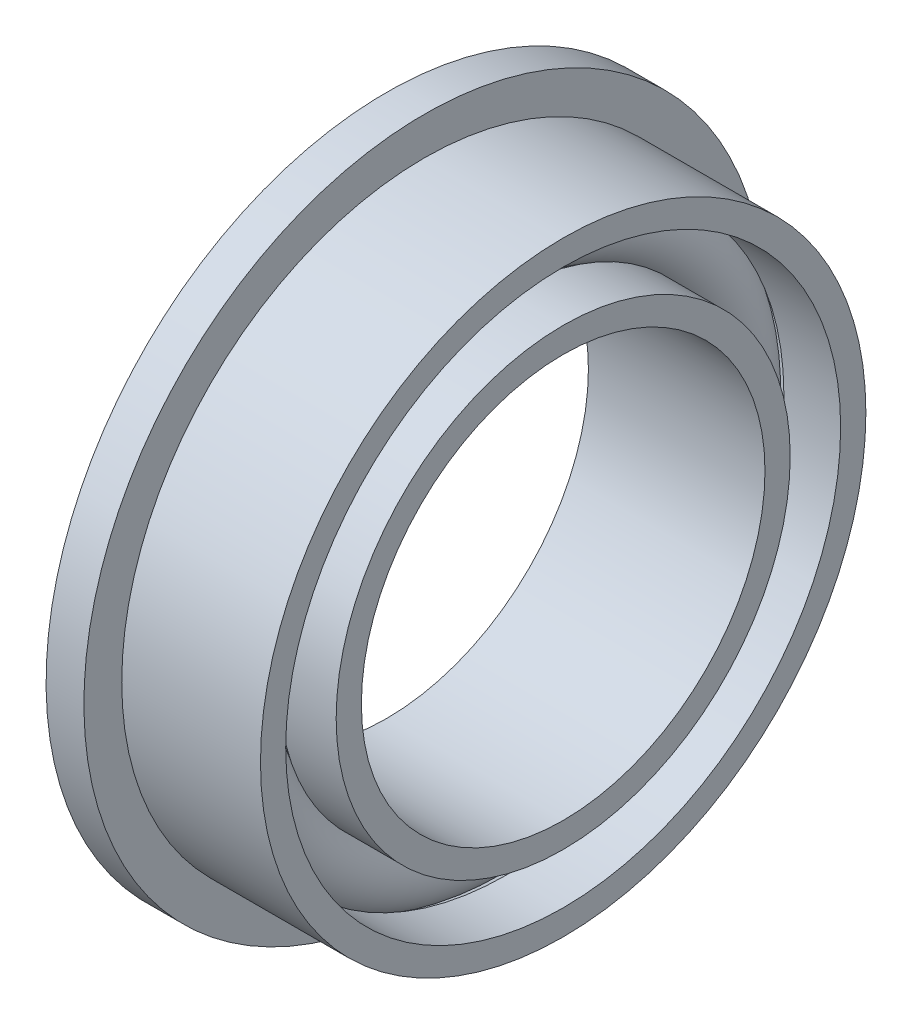
SolidWorks part; units mm, degrees
ref_plane "Front Plane" through (0, 0, 0) normal (0, 0, 1) x (1, 0, 0)
ref_plane "Top Plane" through (0, 0, 0) normal (0, 1, 0) x (1, 0, 0)
ref_plane "Right Plane" through (0, 0, 0) normal (1, 0, 0) x (0, 0, -1)
sketch "Sketch1" plane through (0, 0, 0) normal (0, 0, 1) x (1, 0, 0)
  line L0 (-42.1112, 0) -> (42.1112, 0) construction
  line L1 (0, 39.1762) -> (0, -39.1762) construction
  line L2 (-1, 6.75) -> (-1, 6)
  line L3 (-1, 6) -> (1.75, 6)
  line L4 (-1.75, 6.75) -> (-1, 6.75)
  line L5 (1.75, 6) -> (1.75, 5.5)
  line L6 (1.75, 5.5) -> (0.6245, 5.5)
  line L7 (-0.6245, 5.5) -> (-1.75, 5.5)
  line L8 (-1.75, 5.5) -> (-1.75, 6.75)
  line L9 (-1.75, 4.5) -> (-1.75, 4)
  line L10 (-1.75, 4) -> (1.75, 4)
  line L11 (1.75, 4) -> (1.75, 4.5)
  line L12 (1.75, 4.5) -> (0.6245, 4.5)
  line L13 (-0.6245, 4.5) -> (-1.75, 4.5)
  line L14 (-3.4412, 5) -> (7.4789, 5) construction
  arc A0 (0.6245, 5.5) -> (-0.6245, 5.5) centre (0, 5) ccw
  arc A1 (0.6245, 4.5) -> (-0.6245, 4.5) centre (0, 5) cw
  circle A2 centre (0, 5) radius 0.75
  dimension "D4" = 1.5
  dimension "D10" = 0.8
  dimension "D5" = 0.75
  dimension "D6" = 13.5
  dimension "D2" = 4
  dimension "D3" = 0.5
  dimension "D7" = 3.5
  dimension "D8" = 12
revolve "Revolve1" add sketch "Sketch1" angle 360 about L0 region at (-0.377, 5.9376, 0) region at (-1.1872, 4.4646, 0)
revolve "Revolve2" add sketch "Sketch1<3>" angle 360 about L0 region at (0, 5, 0)
sketch "Sketch1<3>" plane through (0, 0, 0) normal (0, 0, 1) x (1, 0, 0) same geometry as "Sketch1"
